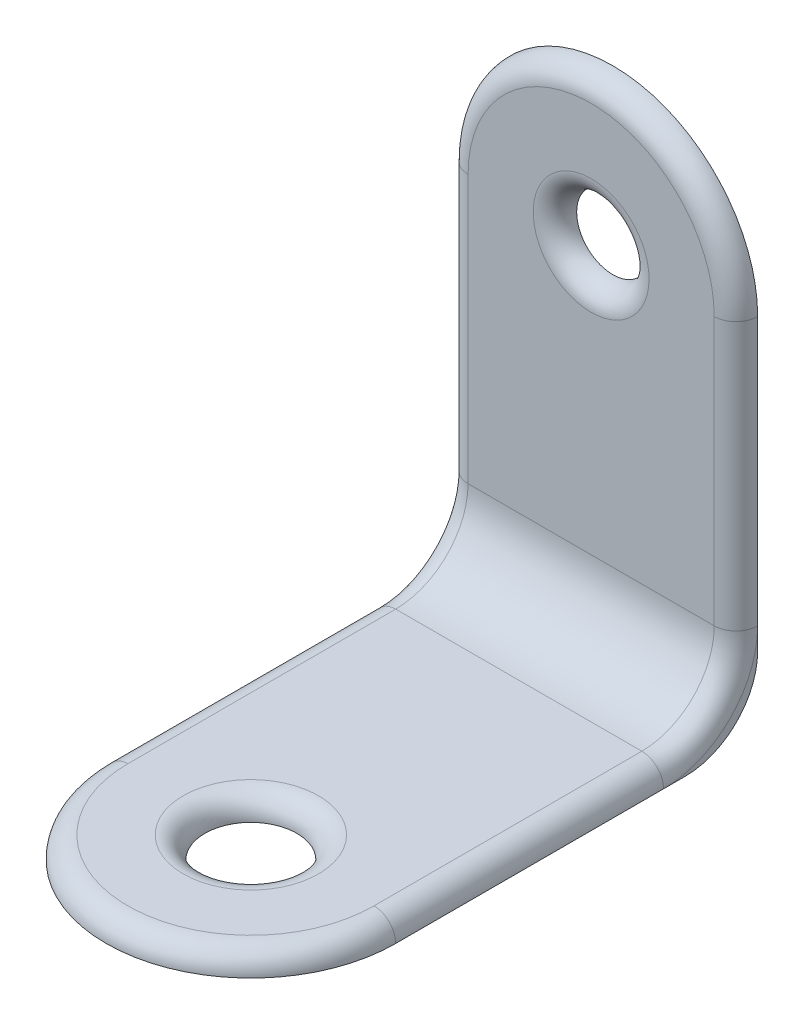
SolidWorks part; units mm, degrees
ref_plane "Front Plane" through (0, 0, 0) normal (0, 0, 1) x (1, 0, 0)
ref_plane "Top Plane" through (0, 0, 0) normal (0, 1, 0) x (1, 0, 0)
ref_plane "Right Plane" through (0, 0, 0) normal (1, 0, 0) x (0, 0, -1)
sketch "Sketch1" plane through (0, 0, 0) normal (0, 1, 0) x (1, 0, 0)
  line L0 (-20, 0) -> (-20, 50)
  line L1 (-20, 50) -> (20, 50)
  line L2 (20, 50) -> (20, 0)
  circle A0 centre (0, 0) radius 6.35
  circle A1 centre (0, 0) radius 20
  dimension "D1" = 12.7
  dimension "D2" = 40
  dimension "D3" = 50
extrude "Boss-Extrude1" add sketch "Sketch1" along normal blind 3 contours A1 L2 L1 L0 | A1 A0 region at (0, 0, -32.5634) region at (0, 0, -19.4343)
sketch "Sketch2" plane through (0, 0, -50) normal (0, 0, -1) x (-1, 0, 0)
  line L0 (-20, 3) -> (-20, 50)
  line L1 (20, 50) -> (20, 3)
  line L4 (-20, 0) -> (20, 0)
  line L5 (20, 0) -> (20, 3)
  line L6 (20, 3) -> (-20, 3)
  line L7 (-20, 3) -> (-20, 0)
  line L8 (-20, 0) -> (20, 0)
  line L9 (20, 0) -> (20, 3)
  line L11 (-20, 3) -> (-20, 0)
  arc A0 (-20, 50) -> (20, 50) centre (0, 50) cw
  circle A1 centre (0, 50) radius 5
  dimension "D2" = 50
  dimension "D3" = 10
  dimension "D1" = 0
extrude "Boss-Extrude2" add sketch "Sketch2" against normal blind 3
fillet "Fillet1" radius 10 1 edges at (0, 3, -47)
fillet "Fillet2" radius 10 1 edges at (0, 0, -50)
fillet "Fillet3" radius 3 9 edges at (20, 5.9289, -44.0711) (20, 31.5, -47) (0, 70, -47) (-20, 31.5, -47) (-20, 5.9289, -44.0711) (0, 3, 6.35) (0, 3, 20) (-20, 3, -18.5) (20, 3, -18.5)
fillet "Fillet4" radius 3 1 edges at (-5, 50, -47)
